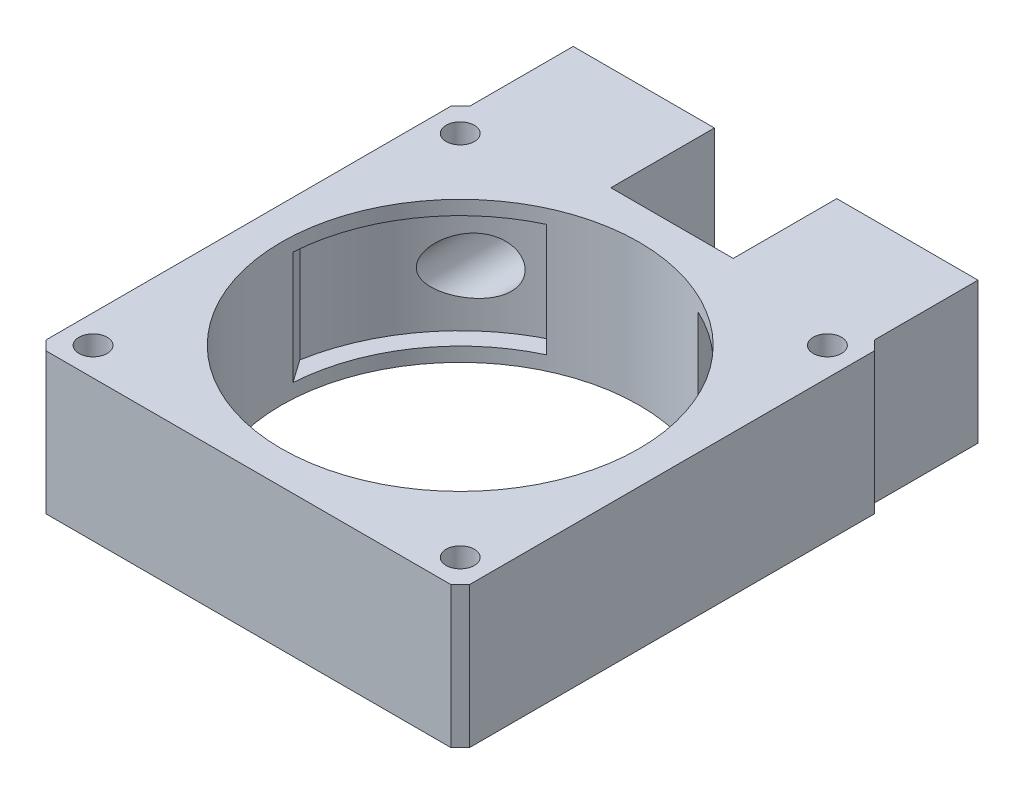
SolidWorks part; units mm, degrees
ref_plane "前视基准面" through (0, 0, 0) normal (0, 0, 1) x (1, 0, 0)
ref_plane "上视基准面" through (0, 0, 0) normal (0, 1, 0) x (1, 0, 0)
ref_plane "右视基准面" through (0, 0, 0) normal (1, 0, 0) x (0, 0, -1)
sketch "草图1" plane through (0, 0, 0) normal (0, 1, 0) x (1, 0, 0)
  line L1 (-22.5, -22.5) -> (22.5, -22.5)
  line L2 (-22.5, -22.5) -> (-22.5, 22.5)
  line L3 (-22.5, 22.5) -> (22.5, 22.5)
  line L4 (22.5, -22.5) -> (22.5, 22.5)
  line L5 (-22.5, -22.5) -> (22.5, 22.5) construction
  line L6 (-22.5, 22.5) -> (22.5, -22.5) construction
  point P0 (0, 0)
  dimension "D1" = 45
  dimension "D2" = 45
extrude "凸台-拉伸1" add sketch "草图1" along normal blind 15
sketch "草图2" plane through (0, 15, 0) normal (0, 1, 0) x (1, 0, 0)
  circle A0 centre (0, 0) radius 19
  dimension "D1" = 38
extrude "切除-拉伸1" cut sketch "草图2" against normal through all
sketch "草图3" plane through (0, 15, 0) normal (0, 1, 0) x (1, 0, 0)
  circle A0 centre (0, 0) radius 20
  circle A1 centre (0, 0) radius 21.5
  dimension "D1" = 40
  dimension "D2" = 43
extrude "切除-拉伸2" [suppressed] cut sketch "草图3" against normal blind 0.4
sketch "草图4" plane through (0, 0, 0) normal (0, -1, 0) x (1, 0, 0)
  circle A1 centre (0, 0) radius 21.5
  circle A2 centre (0, 0) radius 21.5
  circle A3 centre (0, 0) radius 20
  circle A4 centre (0, 0) radius 20
  dimension "D1" = 0
  dimension "D2" = 0
extrude "切除-拉伸3" [suppressed] cut sketch "草图4" against normal blind 0.4
sketch "草图5" plane through (0, 0, -22.5) normal (0, 0, -1) x (-1, 0, 0)
  line L0 (0, 15) -> (0, 0) construction
  line L1 (-22.5, 15) -> (22.5, 15) construction
  line L2 (-14, 15) -> (-14, 0) construction
  line L3 (-22.5, 0) -> (22.5, 0) construction
  line L4 (21.5, 15) -> (6.5, 15)
  line L5 (-21.5, 0) -> (-6.5, 0)
  line L6 (-21.5, 0) -> (-21.5, 15)
  line L7 (-21.5, 15) -> (-6.5, 15)
  line L8 (-6.5, 0) -> (-6.5, 15)
  line L9 (-21.5, 0) -> (-6.5, 15) construction
  line L10 (-21.5, 15) -> (-6.5, 0) construction
  line L11 (6.5, 0) -> (6.5, 15)
  line L12 (21.5, 0) -> (6.5, 0)
  line L13 (21.5, 0) -> (21.5, 15)
  point P9 (-14, 7.5)
  dimension "D1" = 15
  dimension "D2" = 14
extrude "凸台-拉伸2" add sketch "草图5" along normal blind 12
sketch "草图6" plane through (0, 0, -34.5) normal (0, 0, -1) x (-1, 0, 0)
  line L0 (-14, 15) -> (-14, 0) construction
  line L1 (-6.5, 15) -> (-21.5, 15) construction
  line L2 (-21.5, 0) -> (-6.5, 0) construction
  line L3 (-21.5, 7.5) -> (-6.5, 7.5) construction
  line L4 (-21.5, 15) -> (-21.5, 0) construction
  line L5 (-6.5, 0) -> (-6.5, 15) construction
  line L6 (0, 15) -> (0, 0) construction
  line L7 (-6.5, 15) -> (6.5, 15) construction
  circle A0 centre (-14, 7.5) radius 3
  circle A1 centre (14, 7.5) radius 3
  dimension "D1" = 6
extrude "切除-拉伸4" cut sketch "草图6" against normal blind 35
sketch "草图7" plane through (0, 15, 0) normal (0, 1, 0) x (1, 0, 0)
  line L0 (-21.5, 22.5) -> (-22.5, 22.5) construction
  line L1 (-22.5, 22.5) -> (-22.5, -22.5) construction
  line L2 (0, 22.5) -> (0, -22.5) construction
  line L3 (6.5, 22.5) -> (-6.5, 22.5) construction
  line L4 (-22.5, -22.5) -> (22.5, -22.5) construction
  line L5 (-22.5, 0) -> (22.5, 0) construction
  line L6 (22.5, -22.5) -> (22.5, 22.5) construction
  circle A0 centre (-19.5, 19.5) radius 1.5
  circle A1 centre (19.5, 19.5) radius 1.5
  circle A2 centre (19.5, -19.5) radius 1.5
  circle A3 centre (-19.5, -19.5) radius 1.5
  dimension "D1" = 3
  dimension "D2" = 3
  dimension "D3" = 3
extrude "切除-拉伸5" cut sketch "草图7" against normal through all
ref_plane "基准面1" through (0, 7.5, 0) normal (0, -1, 0) x (-1, 0, 0)
sketch "草图8" plane through (0, 7.5, 0) normal (0, -1, 0) x (-1, 0, 0)
  line L0 (0, 0) -> (0, 22.5) construction
  line L1 (-6.5, 22.5) -> (6.5, 22.5) construction
  line L2 (0, 0) -> (-8.875, 19.0325) construction
  line L3 (-20.681, 3.6466) -> (0, 0) construction
  line L4 (-8.875, 19.0325) -> (-8.0297, 17.2198)
  line L5 (-20.681, 3.6466) -> (-18.7113, 3.2993)
  line L6 (20.681, 3.6466) -> (18.7113, 3.2993)
  line L7 (8.875, 19.0325) -> (8.0297, 17.2198)
  arc A0 (-8.0297, 17.2198) -> (-18.7113, 3.2993) centre (0, 0) ccw
  circle A1 centre (0, 0) radius 19 construction
  arc A2 (-8.875, 19.0325) -> (-20.681, 3.6466) centre (0, 0) ccw
  arc A3 (8.875, 19.0325) -> (20.681, 3.6466) centre (0, 0) cw
  arc A4 (8.0297, 17.2198) -> (18.7113, 3.2993) centre (0, 0) cw
  dimension "D1" = 21
  dimension "D2" = 25
  dimension "D3" = 80
extrude "切除-拉伸6" cut sketch "草图8" against normal blind 6 and the other way blind 6
sketch "草图9" plane through (0, 0, -34.5) normal (0, 0, -1) x (-1, 0, 0)
  circle A0 centre (-14, 7.5) radius 4.25
  circle A1 centre (14, 7.5) radius 4.25
  dimension "D1" = 8.5
  dimension "D2" = 8.5
extrude "切除-拉伸7" cut sketch "草图9" against normal blind 12
chamfer "倒角1" distance 2 angle 45 2 edges at (-18.7113, 7.5, -3.2993) (18.7113, 7.5, -3.2993)
chamfer "倒角2" distance 1 angle 45 4 edges at (22.5, 7.5, 22.5) (-22.5, 7.5, 22.5) (-22.5, 7.5, -22.5) (22.5, 7.5, -22.5)
chamfer "倒角3" distance 1 angle 45 2 edges at (-18.25, 7.5, -22.5) (9.75, 7.5, -22.5)
chamfer "倒角4" distance 1 angle 45 8 edges at (-14, 0, -34.5) (-21.5, 7.5, -34.5) (-14, 15, -34.5) (-6.5, 7.5, -34.5) (14, 0, -34.5) (6.5, 7.5, -34.5) (14, 15, -34.5) (21.5, 7.5, -34.5)
